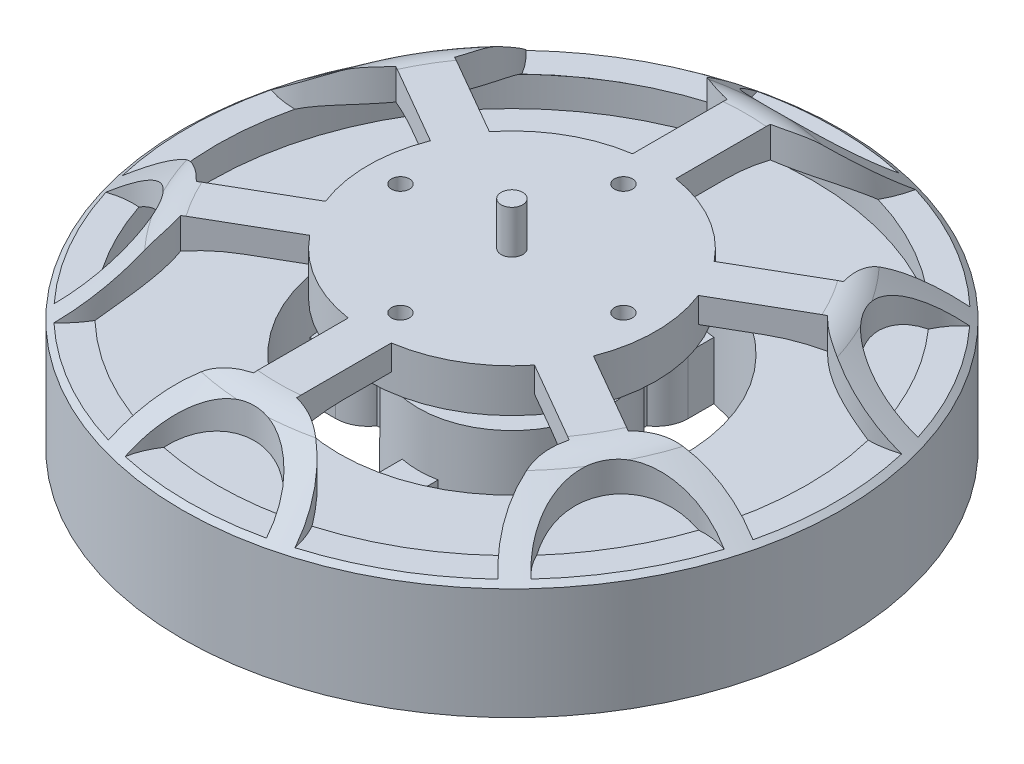
SolidWorks part; units mm, degrees
ref_plane "Front Plane" through (0, 0, 0) normal (0, 0, 1) x (1, 0, 0)
ref_plane "Top Plane" through (0, 0, 0) normal (0, 1, 0) x (1, 0, 0)
ref_plane "Right Plane" through (0, 0, 0) normal (1, 0, 0) x (0, 0, -1)
ref_axis "Axis1" through (0, 40.089, 0) along (0, -1, 0)
sketch "Sketch1" plane through (0, 0, 0) normal (0, 0, 1) x (1, 0, 0)
  line L0 (0, 0) -> (9.65, 0)
  line L1 (9.65, 0) -> (9.65, 3.93)
  line L2 (9.65, 3.93) -> (27.5, 3.93)
  line L3 (27.5, 3.93) -> (45.83, 8.08)
  line L4 (45.83, 8.08) -> (45.83, 23.58)
  line L5 (45.83, 23.58) -> (36.1322, 30.9557)
  line L6 (32.5, 32.18) -> (1.5, 32.18)
  line L7 (1.5, 32.18) -> (1.5, 38.18)
  line L8 (1.5, 38.18) -> (0, 38.18)
  line L9 (0, 38.18) -> (0, 0) construction
  line L10 (0, 0) -> (0, 38.18)
  arc A0 (36.1322, 30.9557) -> (32.5, 32.18) centre (32.5, 26.18) ccw
  dimension "D10" = 6
  dimension "D1" = 3
  dimension "D2" = 6
  dimension "D3" = 28.25
  dimension "D4" = 3.93
  dimension "D5" = 19.3
  dimension "D6" = 4.15
  dimension "D7" = 91.66
  dimension "D8" = 55
  dimension "D9" = 65
  dimension "D11" = 15.5
revolve "Revolve1" add sketch "Sketch1" angle 360 about L9
sketch "Sketch2" plane through (0, 3.93, 0) normal (0, -1, 0) x (1, 0, 0)
  line L0 (0, 0) -> (0, 27.5) construction
  line L1 (2.5, 12.7574) -> (2.5, 16.2583)
  line L2 (4.5, 20) -> (4.5, 23.5744)
  line L3 (0, 0) -> (16.9706, 16.9706) construction
  line L4 (20, 4.5) -> (23.5744, 4.5)
  line L5 (12.7574, 2.5) -> (16.2583, 2.5)
  line L6 (20, -4.5) -> (23.5744, -4.5)
  line L7 (4.5, -20) -> (4.5, -23.5744)
  line L8 (2.5, -12.7574) -> (2.5, -16.2583)
  line L9 (12.7574, -2.5) -> (16.2583, -2.5)
  line L10 (-4.5, -20) -> (-4.5, -23.5744)
  line L11 (-20, -4.5) -> (-23.5744, -4.5)
  line L12 (-12.7574, -2.5) -> (-16.2583, -2.5)
  line L13 (-2.5, -12.7574) -> (-2.5, -16.2583)
  line L14 (-20, 4.5) -> (-23.5744, 4.5)
  line L15 (-4.5, 20) -> (-4.5, 23.5744)
  line L16 (-2.5, 12.7574) -> (-2.5, 16.2583)
  line L17 (-12.7574, 2.5) -> (-16.2583, 2.5)
  arc A0 (4.5, 23.5744) -> (23.5744, 4.5) centre (0, 0) cw
  arc A1 (4.5, 20) -> (2.5, 16.2583) centre (0, 20) cw
  arc A2 (2.5, 12.7574) -> (12.7574, 2.5) centre (0, 0) cw
  circle A3 centre (0, 0) radius 27.5 construction
  arc A4 (20, 4.5) -> (16.2583, 2.5) centre (20, 0) ccw
  arc A5 (20, -4.5) -> (16.2583, -2.5) centre (20, 0) cw
  arc A6 (23.5744, -4.5) -> (4.5, -23.5744) centre (0, 0) cw
  arc A7 (4.5, -20) -> (2.5, -16.2583) centre (0, -20) ccw
  arc A8 (12.7574, -2.5) -> (2.5, -12.7574) centre (0, 0) cw
  arc A9 (-4.5, -20) -> (-2.5, -16.2583) centre (0, -20) cw
  arc A10 (-4.5, -23.5744) -> (-23.5744, -4.5) centre (0, 0) cw
  arc A11 (-20, -4.5) -> (-16.2583, -2.5) centre (-20, 0) ccw
  arc A12 (-2.5, -12.7574) -> (-12.7574, -2.5) centre (0, 0) cw
  arc A13 (-20, 4.5) -> (-16.2583, 2.5) centre (-20, 0) cw
  arc A14 (-23.5744, 4.5) -> (-4.5, 23.5744) centre (0, 0) cw
  arc A15 (-4.5, 20) -> (-2.5, 16.2583) centre (0, 20) ccw
  arc A16 (-12.7574, 2.5) -> (-2.5, 12.7574) centre (0, 0) cw
  point P4 (0, 20)
  point P51 (0, 0)
  dimension "D2" = 13
  dimension "D5" = 24
  dimension "D1" = 20
  dimension "D3" = 5
  dimension "D4" = 9
  dimension "D6" = 45
  dimension "D7" = 4
hole_wizard "M4x0.7 Tapped Hole1" positions "3DSketch1" profile "Sketch4" tap size "M4x0.7" standard "ANSI Metric"
sketch3d "3DSketch1"
  point P0 (-20, 3.93, 0)
  point P3 (0, 3.93, 20)
  point P6 (20, 3.93, 0)
  point P9 (0, 3.93, -20)
sketch "Sketch4" plane through (-20, 3.93, 0) normal (1, 0, 0) x (0, 0, -1)
  line L0 (0, 0) -> (0, 8.9914)
  line L1 (0, 8.9914) -> (1.65, 8)
  line L2 (1.65, 8) -> (1.65, 0)
  line L5 (1.65, 0) -> (0, 0)
  line L10 (0, 8.9914) -> (-1.65, 8) construction
  line L11 (0, -6.35) -> (0, 107.95) construction
  dimension "Tap Drill Dia." = 3.3
  dimension "Tap Drill Depth" = 8
  dimension "Drill Angle" = 118
cosmetic thread "Hole Thread1" parameters "D1"=7.874, "D2"=4
cosmetic thread "Hole Thread2" parameters "D1"=7.874, "D2"=4
cosmetic thread "Hole Thread3" parameters "D1"=7.874, "D2"=4
cosmetic thread "Hole Thread4" parameters "D1"=7.874, "D2"=4
extrude "Cut-Extrude1" cut sketch "Sketch2" against normal blind 8
sketch "Sketch5" plane through (0, 0, 0) normal (0, 0, 1) x (1, 0, 0)
  line L0 (24, 19.43) -> (41.83, 19.43)
  line L1 (-27.5, 3.93) -> (27.5, 3.93) construction
  line L2 (41.83, 19.43) -> (41.83, 23.58)
  line L3 (45.83, 8.08) -> (45.83, 23.58) construction
  line L4 (10, 19.43) -> (13, 19.43)
  line L5 (13, 19.43) -> (13, 11.93)
  line L6 (13, 11.93) -> (24, 11.93)
  line L7 (24, 11.93) -> (24, 19.43)
  line L8 (0, 40.089) -> (0, -1.909) construction
  line L9 (4.5, 11.93) -> (23.5744, 11.93) construction
  line L10 (45.83, 23.58) -> (-45.83, 23.58) construction
  line L11 (20, 28.68) -> (26.6996, 28.68)
  line L12 (32.5, 32.18) -> (-32.5, 32.18) construction
  line L13 (41.83, 23.58) -> (45.83, 20.5378) construction
  line L14 (45.83, 23.58) -> (36.1322, 30.9557) construction
  line L15 (20, 28.68) -> (20, 26.18)
  line L16 (20, 26.18) -> (10, 26.18)
  line L17 (10, 26.18) -> (10, 19.43)
  arc A0 (26.6996, 28.68) -> (41.83, 23.58) centre (26.6996, 3.6861) cw
  dimension "D1" = 15.5
  dimension "D2" = 4
  dimension "D3" = 13
  dimension "D4" = 24
  dimension "D5" = 3.5
  dimension "D6" = 20
  dimension "D7" = 6
  dimension "D8" = 10
revolve "Cut-Revolve3" cut sketch "Sketch5" angle 360 about axis through (0, 40.089, 0) along (0, -1, 0)
sketch "Sketch6" plane through (0, 0, 0) normal (0, 1, 0) x (1, 0, 0)
  line L0 (-3, 19.7737) -> (-3, 32.9241)
  line L1 (3, 19.7737) -> (3, 32.9241)
  line L2 (-3, 19.7737) -> (3, 19.7737) construction
  line L3 (0, 45.83) -> (0, 35.83) construction
  line L4 (15.6245, 12.4849) -> (27.0131, 19.0601)
  line L5 (18.6245, 7.2888) -> (30.0131, 13.864)
  line L6 (15.6245, 12.4849) -> (18.6245, 7.2888) construction
  line L7 (39.6899, 22.915) -> (31.0297, 17.915) construction
  line L8 (18.6245, -7.2888) -> (30.0131, -13.864)
  line L9 (15.6245, -12.4849) -> (27.0131, -19.0601)
  line L10 (18.6245, -7.2888) -> (15.6245, -12.4849) construction
  line L11 (39.6899, -22.915) -> (31.0297, -17.915) construction
  line L12 (3, -19.7737) -> (3, -32.9241)
  line L13 (-3, -19.7737) -> (-3, -32.9241)
  line L14 (3, -19.7737) -> (-3, -19.7737) construction
  line L15 (0, -45.83) -> (0, -35.83) construction
  line L16 (-15.6245, -12.4849) -> (-27.0131, -19.0601)
  line L17 (-18.6245, -7.2888) -> (-30.0131, -13.864)
  line L18 (-15.6245, -12.4849) -> (-18.6245, -7.2888) construction
  line L19 (-39.6899, -22.915) -> (-31.0297, -17.915) construction
  line L20 (-18.6245, 7.2888) -> (-30.0131, 13.864)
  line L21 (-15.6245, 12.4849) -> (-27.0131, 19.0601)
  line L22 (-18.6245, 7.2888) -> (-15.6245, 12.4849) construction
  line L23 (-39.6899, 22.915) -> (-31.0297, 17.915) construction
  line L24 (0, 15.5) -> (15.5, 0) construction
  line L25 (15.5, 0) -> (0, -15.5) construction
  line L26 (0, -15.5) -> (-15.5, 0) construction
  line L27 (-15.5, 0) -> (0, 15.5) construction
  arc A1 (-9.9403, 44.739) -> (9.9403, 44.739) centre (0, 45.83) ccw
  circle A2 centre (0, 0) radius 45.83 construction
  arc A3 (-13.1108, 43.9146) -> (-3, 32.9241) centre (0, 45.83) ccw
  arc A4 (13.1108, 43.9146) -> (3, 32.9241) centre (0, 45.83) cw
  arc A5 (-13.1108, 43.9146) -> (-9.9403, 44.739) centre (0, 0) cw
  arc A6 (9.9403, 44.739) -> (13.1108, 43.9146) centre (0, 0) cw
  arc A7 (33.775, 30.9781) -> (43.7153, 13.7609) centre (39.6899, 22.915) ccw
  arc A8 (31.4758, 33.3116) -> (27.0131, 19.0601) centre (39.6899, 22.915) ccw
  arc A9 (44.5866, 10.603) -> (30.0131, 13.864) centre (39.6899, 22.915) cw
  arc A10 (31.4758, 33.3116) -> (33.775, 30.9781) centre (0, 0) cw
  arc A11 (43.7153, 13.7609) -> (44.5866, 10.603) centre (0, 0) cw
  arc A12 (43.7153, -13.7609) -> (33.775, -30.9781) centre (39.6899, -22.915) ccw
  arc A13 (44.5866, -10.603) -> (30.0131, -13.864) centre (39.6899, -22.915) ccw
  arc A14 (31.4758, -33.3116) -> (27.0131, -19.0601) centre (39.6899, -22.915) cw
  arc A15 (44.5866, -10.603) -> (43.7153, -13.7609) centre (0, 0) cw
  arc A16 (33.775, -30.9781) -> (31.4758, -33.3116) centre (0, 0) cw
  arc A17 (9.9403, -44.739) -> (-9.9403, -44.739) centre (0, -45.83) ccw
  arc A18 (13.1108, -43.9146) -> (3, -32.9241) centre (0, -45.83) ccw
  arc A19 (-13.1108, -43.9146) -> (-3, -32.9241) centre (0, -45.83) cw
  arc A20 (13.1108, -43.9146) -> (9.9403, -44.739) centre (0, 0) cw
  arc A21 (-9.9403, -44.739) -> (-13.1108, -43.9146) centre (0, 0) cw
  arc A22 (-33.775, -30.9781) -> (-43.7153, -13.7609) centre (-39.6899, -22.915) ccw
  arc A23 (-31.4758, -33.3116) -> (-27.0131, -19.0601) centre (-39.6899, -22.915) ccw
  arc A24 (-44.5866, -10.603) -> (-30.0131, -13.864) centre (-39.6899, -22.915) cw
  arc A25 (-31.4758, -33.3116) -> (-33.775, -30.9781) centre (0, 0) cw
  arc A26 (-43.7153, -13.7609) -> (-44.5866, -10.603) centre (0, 0) cw
  arc A27 (-43.7153, 13.7609) -> (-33.775, 30.9781) centre (-39.6899, 22.915) ccw
  arc A28 (-44.5866, 10.603) -> (-30.0131, 13.864) centre (-39.6899, 22.915) ccw
  arc A29 (-31.4758, 33.3116) -> (-27.0131, 19.0601) centre (-39.6899, 22.915) cw
  arc A30 (-44.5866, 10.603) -> (-43.7153, 13.7609) centre (0, 0) cw
  arc A31 (-33.775, 30.9781) -> (-31.4758, 33.3116) centre (0, 0) cw
  arc A32 (3, 19.7737) -> (15.6245, 12.4849) centre (0, 0) cw
  arc A33 (18.6245, 7.2888) -> (18.6245, -7.2888) centre (0, 0) cw
  arc A34 (15.6245, -12.4849) -> (3, -19.7737) centre (0, 0) cw
  arc A35 (-3, -19.7737) -> (-15.6245, -12.4849) centre (0, 0) cw
  arc A36 (-18.6245, -7.2888) -> (-18.6245, 7.2888) centre (0, 0) cw
  arc A37 (-3, 19.7737) -> (-15.6245, 12.4849) centre (0, 0) ccw
  point P0 (0, 19.7737)
  point P17 (0, 15.5)
  point P28 (15.5, 0)
  point P38 (0, -15.5)
  point P68 (0, 0)
  point P69 (-15.5, 0)
  dimension "D1" = 6
  dimension "D3" = 3.25
  dimension "D5" = 20
  dimension "D2" = 6
  dimension "D4" = 10
  dimension "D6" = 15.5
extrude "Cut-Extrude3" cut sketch "Sketch6" against normal blind 8 from surface flip side to cut starting at face at (0, 32.18, 1.5)
hole_wizard "M3x0.5 Tapped Hole1" positions "Sketch8" profile "Sketch10" tap size "M3x0.5" standard "ANSI Metric" end condition up to next
sketch "Sketch8" plane through (0, 32.18, 0) normal (0, 1, 0) x (1, 0, 0)
  point P0 (0, 15.5)
  point P3 (15.5, 0)
  point P6 (0, -15.5)
  point P9 (-15.5, 0)
sketch "Sketch10" plane through (0, 32.18, -15.5) normal (1, 0, 0) x (0, 0, 1)
  line L0 (0, 0) -> (0, 6)
  line L1 (0, 6) -> (1.25, 6)
  line L2 (1.25, 6) -> (1.25, 0)
  line L5 (1.25, 0) -> (0, 0)
  line L11 (0, -6.35) -> (0, 107.95) construction
  dimension "Thru Tap Drill Dia." = 2.5
  dimension "Thru Tap Drill Depth" = 6
cosmetic thread "Hole Thread5" parameters "D2"=3
cosmetic thread "Hole Thread6" parameters "D2"=3
cosmetic thread "Hole Thread7" parameters "D2"=3
cosmetic thread "Hole Thread8" parameters "D2"=3
equation "\"INTERIOR_STATOR_BORE_OD\"= 48MM"
equation "\"INTERIOR_STATOR_BORE_ID\"= 26mm"
equation "\"D5@Sketch2\"=\"INTERIOR_STATOR_BORE_OD\"/2"
equation "\"D2@Sketch2\"=\"INTERIOR_STATOR_BORE_ID\"/2"
equation "\"D3@Sketch5\"=\"INTERIOR_STATOR_BORE_ID\"/2"
equation "\"D4@Sketch5\"=\"INTERIOR_STATOR_BORE_OD\"/2"
